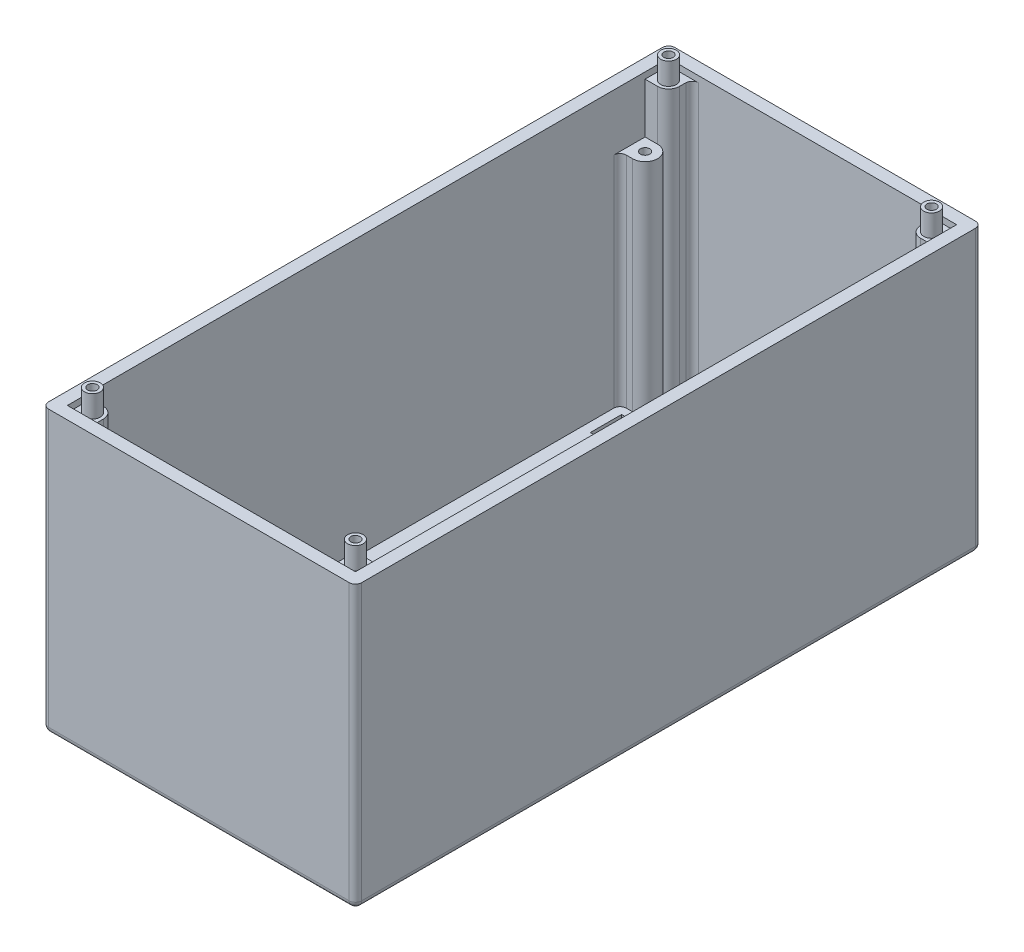
SolidWorks part; units mm, degrees
ref_plane "Front Plane" through (0, 0, 0) normal (0, 0, 1) x (1, 0, 0)
ref_plane "Top Plane" through (0, 0, 0) normal (0, 1, 0) x (1, 0, 0)
ref_plane "Right Plane" through (0, 0, 0) normal (1, 0, 0) x (0, 0, -1)
sketch "Sketch1" plane through (0, 0, 0) normal (0, 1, 0) x (1, 0, 0)
  line L1 (50, -100) -> (-50, -100)
  line L2 (50, -100) -> (50, 100)
  line L3 (50, 100) -> (-50, 100)
  line L4 (-50, -100) -> (-50, 100)
  line L5 (50, -100) -> (-50, 100) construction
  line L6 (50, 100) -> (-50, -100) construction
  point P0 (0, 0)
  dimension "D1" = 200
  dimension "D2" = 100
extrude "Boss-Extrude1" add sketch "Sketch1" along normal blind 2
sketch "Sketch3" plane through (0, 2, 0) normal (0, 1, 0) x (1, 0, 0)
  line L1 (-50, 100) -> (50, 100)
  line L2 (-50, 100) -> (-50, -100)
  line L3 (-50, -100) -> (50, -100)
  line L4 (50, 100) -> (50, -100)
  line L5 (-46, 96) -> (-46, -96)
  line L6 (-46, -96) -> (46, -96)
  line L7 (46, 96) -> (46, -96)
  line L8 (-46, 96) -> (46, 96)
  point P25 (-50, 100)
  dimension "D1" = 4
extrude "Boss-Extrude2" add sketch "Sketch3" along normal blind 88
sketch "Sketch16" plane through (0, 2, 0) normal (0, 1, 0) x (1, 0, 0)
  line L0 (46, 96) -> (-46, 96) construction
  line L1 (-46, -96) -> (46, -96) construction
  line L2 (-46, 96) -> (-46, -96) construction
  line L3 (-46, 96) -> (-46, -96) construction
  line L4 (46, 96) -> (-46, 96) construction
  line L8 (46, -96) -> (46, 96) construction
  line L9 (-46, -96) -> (46, -96) construction
  line L11 (46, -96) -> (46, 96) construction
  circle A4 centre (-42, 92) radius 3.5
  circle A5 centre (42, 92) radius 3.5
  circle A6 centre (42, -92) radius 3.5
  circle A7 centre (-42, -92) radius 3.5
  dimension "D1" = 4
  dimension "D2" = 4
  dimension "D4" = 4
  dimension "D7" = 7
  dimension "D3" = 4
  dimension "D5" = 4
  dimension "D6" = 4
  dimension "D8" = 4
  dimension "D9" = 4
extrude "Boss-Extrude3" add sketch "Sketch16" along normal blind 86
fillet "Fillet2" radius 2 4 edges at (50, 0, 0) (0, 0, 100) (-50, 0, 0) (0, 0, -100)
sketch "Sketch17" plane through (0, 2, 0) normal (0, 1, 0) x (1, 0, 0)
  line L0 (-38.5, 92) -> (-38.5, 96)
  line L1 (46, 96) -> (-46, 96) construction
  line L2 (-38.5, 96) -> (-46, 96)
  line L3 (-46, 96) -> (-46, 88.5)
  line L4 (-46, 96) -> (-46, -96) construction
  line L5 (-46, 88.5) -> (-42, 88.5)
  line L6 (-42, 88.5) -> (-38.5, 92)
  line L7 (38.5, 92) -> (38.5, 96)
  line L8 (46, 96) -> (-46, 96) construction
  line L9 (38.5, 96) -> (46, 96)
  line L10 (46, 96) -> (46, 88.5)
  line L11 (46, -96) -> (46, 96) construction
  line L12 (46, 88.5) -> (42, 88.5)
  line L13 (42, 88.5) -> (38.5, 92)
  line L14 (-38.5, -92) -> (-38.5, -96)
  line L15 (-46, -96) -> (46, -96) construction
  line L16 (-38.5, -96) -> (-46, -96)
  line L17 (-46, -96) -> (-46, -88.5)
  line L18 (-46, 96) -> (-46, -96) construction
  line L19 (-46, -88.5) -> (-42, -88.5)
  line L20 (-42, -88.5) -> (-38.5, -92)
  line L21 (46, -96) -> (38.5, -96)
  line L22 (-46, -96) -> (46, -96) construction
  line L23 (38.5, -96) -> (38.5, -92)
  line L24 (38.5, -92) -> (42, -88.5)
  line L25 (42, -88.5) -> (46, -88.5)
  line L26 (46, -96) -> (46, 96) construction
  line L27 (46, -88.5) -> (46, -96)
  circle A0 centre (-42, 92) radius 3.5 construction
  circle A1 centre (-42, 92) radius 3.5 construction
  circle A2 centre (42, 92) radius 3.5 construction
  circle A3 centre (42, 92) radius 3.5 construction
  circle A4 centre (-42, -92) radius 3.5 construction
  circle A5 centre (-42, -92) radius 3.5 construction
  circle A6 centre (42, -92) radius 3.5 construction
  circle A7 centre (42, -92) radius 3.5 construction
  dimension "D1" = 4
  dimension "D2" = 4
  dimension "D3" = 4
  dimension "D4" = 4
  dimension "D5" = 4
  dimension "D6" = 4
extrude "Boss-Extrude4" add sketch "Sketch17" along normal blind 86
sketch "Sketch20" plane through (0, 2, 0) normal (0, 1, 0) x (1, 0, 0)
  line L0 (-46, 88.5) -> (-42, 88.5)
  line L1 (-46, 88.5) -> (-46, 80.5)
  line L2 (-46, 88.5) -> (-46, -88.5) construction
  line L3 (-46, 80.5) -> (-42, 80.5)
  line L4 (46, 88.5) -> (42, 88.5)
  line L5 (42, 88.5) -> (46, 88.5) construction
  line L6 (46, 88.5) -> (46, 80.5)
  line L7 (46, 80.5) -> (42, 80.5)
  line L8 (-46, -88.5) -> (-42, -88.5)
  line L9 (-46, -88.5) -> (-46, -80.491)
  line L10 (-46, -80.491) -> (-42, -80.491)
  line L11 (46, -88.5) -> (42, -88.5)
  line L12 (46, -88.5) -> (46, -80.5)
  line L13 (46, -96) -> (46, 96) construction
  line L14 (46, -80.5) -> (42, -80.5)
  arc A0 (-42, 88.5) -> (-42, 80.5) centre (-42, 84.5) cw
  circle A1 centre (42, 92) radius 3.5 construction
  arc A2 (42, 88.5) -> (42, 80.5) centre (42, 84.5) ccw
  arc A3 (-42, -80.491) -> (-42, -88.5) centre (-42, -84.4955) cw
  arc A4 (42, -80.5) -> (42, -88.5) centre (42, -84.5) ccw
  dimension "D2" = 4
  dimension "D3" = 4.0045
  dimension "D1" = 8
  dimension "D4" = 8
extrude "Boss-Extrude5" add sketch "Sketch20" along normal blind 70
sketch "Sketch21" plane through (0, 72, 0) normal (0, 1, 0) x (1, 0, 0)
  circle A0 centre (-42, 84.5) radius 1.5
  circle A1 centre (42, 84.5) radius 1.5
  circle A2 centre (42, -84.5) radius 1.5
  circle A3 centre (-42, -84.4955) radius 1.5
  dimension "D1" = 3
  dimension "D2" = 3
  dimension "D3" = 3
  dimension "D4" = 3
extrude "Cut-Extrude3" cut sketch "Sketch21" against normal blind 13
fillet "Fillet4" radius 2 8 edges at (49.4142, 0.5858, 99.4142) (-49.4142, 0.5858, 99.4142) (-49.4142, 0.5858, -99.4142) (49.4142, 0.5858, -99.4142) (50, 46, 100) (-50, 46, 100) (-50, 46, -100) (50, 46, -100)
sketch "Sketch22" plane through (0, 2, 0) normal (0, 1, 0) x (1, 0, 0)
  circle A0 centre (-42, 92) radius 2.75
  circle A1 centre (42, 92) radius 2.75
  circle A2 centre (42, -92) radius 2.75
  circle A3 centre (-42, -92) radius 2.75
  dimension "D1" = 5.5
  dimension "D2" = 5.5
  dimension "D3" = 5.5
  dimension "D4" = 5.5
extrude "Cut-Extrude4" cut sketch "Sketch22" against normal blind 2 and the other way blind 83
sketch "Sketch24" plane through (0, 88, 0) normal (0, 1, 0) x (1, 0, 0)
  circle A0 centre (-42, 92) radius 2.5
  circle A1 centre (42, 92) radius 2.5
  circle A2 centre (42, -92) radius 2.5
  circle A3 centre (-42, -92) radius 2.5
  dimension "D1" = 5
  dimension "D2" = 5
  dimension "D3" = 5
  dimension "D4" = 5
extrude "Boss-Extrude6" add sketch "Sketch24" along normal blind 7
sketch "Sketch25" plane through (0, 85, 0) normal (0, -1, 0) x (1, 0, 0)
  circle A0 centre (-42, 92) radius 1.5
  circle A1 centre (42, 92) radius 1.5
  circle A2 centre (-42, -92) radius 1.5
  circle A3 centre (42, -92) radius 1.5
  dimension "D1" = 3
  dimension "D2" = 3
  dimension "D3" = 3
  dimension "D4" = 3
extrude "Cut-Extrude5" cut sketch "Sketch25" against normal blind 10
fillet "Fillet5" radius 2 8 edges at (46, 37, -80.5) (38.5, 45, -96) (-38.5, 45, -96) (-46, 37, -80.5) (-46, 37, 80.491) (-38.5, 45, 96) (46, 37, 80.5) (38.5, 45, 96)
sketch "Sketch26" plane through (0, 2, 0) normal (0, 1, 0) x (1, 0, 0)
  line L0 (-36.5, -96) -> (36.5, -96) construction
  line L1 (46, -78.5) -> (46, 78.5) construction
  line L2 (-46, 78.5) -> (-46, -78.491) construction
  line L3 (36.5, 96) -> (-36.5, 96) construction
  circle A0 centre (29, -78) radius 3.5
  circle A1 centre (29, -64) radius 3.5
  circle A2 centre (31, 85) radius 3.25
  circle A3 centre (-16, -78) radius 3.5
  dimension "D1" = 7
  dimension "D2" = 7
  dimension "D3" = 18
  dimension "D7" = 6.5
  dimension "D9" = 15
  dimension "D10" = 7
  dimension "D11" = 18
  dimension "D4" = 32
  dimension "D5" = 17
  dimension "D6" = 17
  dimension "D8" = 11
  dimension "D12" = 30
extrude "Cut-Extrude6" cut sketch "Sketch26" against normal blind 2
sketch "Sketch27" plane through (0, 0, 0) normal (0, -1, 0) x (1, 0, 0)
  line L0 (-48, -98) -> (48, -98) construction
  line L1 (-43, -68) -> (-17, -68)
  line L2 (-43, -68) -> (-43, -78)
  line L3 (-43, -78) -> (-17, -78)
  line L4 (-17, -68) -> (-17, -78)
  line L5 (-48, 98) -> (-48, -98) construction
  point P8 (-43, -73)
  dimension "D1" = 26
  dimension "D2" = 10
  dimension "D3" = 20
  dimension "D4" = 5
extrude "Cut-Extrude7" cut sketch "Sketch27" against normal blind 2
sketch "Sketch28" plane through (0, 0, 0) normal (0, -1, 0) x (1, 0, 0)
  line L0 (48, -98) -> (48, 98) construction
  line L2 (39, -62) -> (39, -76)
  line L4 (41, -62) -> (41, -76)
  line L13 (-48, -98) -> (48, -98) construction
  line L15 (34, -62) -> (34, -76)
  line L17 (36, -62) -> (36, -76)
  line L19 (29, -62) -> (29, -76)
  line L21 (31, -62) -> (31, -76)
  line L23 (24, -62) -> (24, -76)
  line L25 (26, -62) -> (26, -76)
  line L27 (19, -62) -> (19, -76)
  line L29 (21, -62) -> (21, -76)
  line L31 (14, -62) -> (14, -76)
  line L33 (16, -62) -> (16, -76)
  line L35 (9, -62) -> (9, -76)
  line L37 (11, -62) -> (11, -76)
  line L39 (4, -62) -> (4, -76)
  line L41 (6, -62) -> (6, -76)
  line L43 (-1, -62) -> (-1, -76)
  line L45 (1, -62) -> (1, -76)
  line L47 (-6, -62) -> (-6, -76)
  line L49 (-4, -62) -> (-4, -76)
  line L50 (39, 33) -> (39, 19)
  line L52 (39, -43) -> (39, -57)
  line L54 (41, -43) -> (41, -57)
  line L56 (34, -43) -> (34, -57)
  line L58 (36, -43) -> (36, -57)
  line L60 (29, -43) -> (29, -57)
  line L62 (31, -43) -> (31, -57)
  line L64 (24, -43) -> (24, -57)
  line L66 (26, -43) -> (26, -57)
  line L68 (19, -43) -> (19, -57)
  line L70 (21, -43) -> (21, -57)
  line L72 (14, -43) -> (14, -57)
  line L74 (16, -43) -> (16, -57)
  line L76 (9, -43) -> (9, -57)
  line L78 (11, -43) -> (11, -57)
  line L80 (4, -43) -> (4, -57)
  line L82 (6, -43) -> (6, -57)
  line L84 (-1, -43) -> (-1, -57)
  line L86 (1, -43) -> (1, -57)
  line L88 (-6, -43) -> (-6, -57)
  line L90 (-4, -43) -> (-4, -57)
  line L92 (39, -24) -> (39, -38)
  line L94 (41, -24) -> (41, -38)
  line L96 (34, -24) -> (34, -38)
  line L98 (36, -24) -> (36, -38)
  line L100 (29, -24) -> (29, -38)
  line L102 (31, -24) -> (31, -38)
  line L104 (24, -24) -> (24, -38)
  line L106 (26, -24) -> (26, -38)
  line L108 (19, -24) -> (19, -38)
  line L110 (21, -24) -> (21, -38)
  line L112 (14, -24) -> (14, -38)
  line L114 (16, -24) -> (16, -38)
  line L116 (9, -24) -> (9, -38)
  line L118 (11, -24) -> (11, -38)
  line L120 (4, -24) -> (4, -38)
  line L122 (6, -24) -> (6, -38)
  line L124 (-1, -24) -> (-1, -38)
  line L126 (1, -24) -> (1, -38)
  line L128 (-6, -24) -> (-6, -38)
  line L130 (-4, -24) -> (-4, -38)
  line L132 (39, -5) -> (39, -19)
  line L134 (41, -5) -> (41, -19)
  line L136 (34, -5) -> (34, -19)
  line L138 (36, -5) -> (36, -19)
  line L140 (29, -5) -> (29, -19)
  line L142 (31, -5) -> (31, -19)
  line L144 (24, -5) -> (24, -19)
  line L146 (26, -5) -> (26, -19)
  line L148 (19, -5) -> (19, -19)
  line L150 (21, -5) -> (21, -19)
  line L152 (14, -5) -> (14, -19)
  line L154 (16, -5) -> (16, -19)
  line L156 (9, -5) -> (9, -19)
  line L158 (11, -5) -> (11, -19)
  line L160 (4, -5) -> (4, -19)
  line L162 (6, -5) -> (6, -19)
  line L164 (-1, -5) -> (-1, -19)
  line L166 (1, -5) -> (1, -19)
  line L168 (-6, -5) -> (-6, -19)
  line L170 (-4, -5) -> (-4, -19)
  line L172 (39, 14) -> (39, 0)
  line L174 (41, 14) -> (41, 0)
  line L176 (34, 14) -> (34, 0)
  line L178 (36, 14) -> (36, 0)
  line L180 (29, 14) -> (29, 0)
  line L182 (31, 14) -> (31, 0)
  line L184 (24, 14) -> (24, 0)
  line L186 (26, 14) -> (26, 0)
  line L188 (19, 14) -> (19, 0)
  line L190 (21, 14) -> (21, 0)
  line L192 (14, 14) -> (14, 0)
  line L194 (16, 14) -> (16, 0)
  line L196 (9, 14) -> (9, 0)
  line L198 (11, 14) -> (11, 0)
  line L200 (4, 14) -> (4, 0)
  line L202 (6, 14) -> (6, 0)
  line L204 (-1, 14) -> (-1, 0)
  line L206 (1, 14) -> (1, 0)
  line L208 (-6, 14) -> (-6, 0)
  line L210 (-4, 14) -> (-4, 0)
  line L211 (41, 33) -> (41, 19)
  line L212 (34, 33) -> (34, 19)
  line L213 (36, 33) -> (36, 19)
  line L214 (29, 33) -> (29, 19)
  line L215 (31, 33) -> (31, 19)
  line L216 (24, 33) -> (24, 19)
  line L217 (26, 33) -> (26, 19)
  line L218 (19, 33) -> (19, 19)
  line L219 (21, 33) -> (21, 19)
  line L220 (14, 33) -> (14, 19)
  line L221 (16, 33) -> (16, 19)
  line L222 (9, 33) -> (9, 19)
  line L223 (11, 33) -> (11, 19)
  line L224 (4, 33) -> (4, 19)
  line L225 (6, 33) -> (6, 19)
  line L226 (-1, 33) -> (-1, 19)
  line L227 (1, 33) -> (1, 19)
  line L228 (-6, 33) -> (-6, 19)
  line L229 (-4, 33) -> (-4, 19)
  line L230 (39, 52) -> (39, 38)
  line L231 (41, 52) -> (41, 38)
  line L232 (34, 52) -> (34, 38)
  line L233 (36, 52) -> (36, 38)
  line L234 (29, 52) -> (29, 38)
  line L235 (31, 52) -> (31, 38)
  line L236 (24, 52) -> (24, 38)
  line L237 (26, 52) -> (26, 38)
  line L238 (19, 52) -> (19, 38)
  line L239 (21, 52) -> (21, 38)
  line L240 (14, 52) -> (14, 38)
  line L241 (16, 52) -> (16, 38)
  line L242 (9, 52) -> (9, 38)
  line L243 (11, 52) -> (11, 38)
  line L244 (4, 52) -> (4, 38)
  line L245 (6, 52) -> (6, 38)
  line L246 (-1, 52) -> (-1, 38)
  line L247 (1, 52) -> (1, 38)
  line L248 (-6, 52) -> (-6, 38)
  line L249 (-4, 52) -> (-4, 38)
  arc A0 (39, -62) -> (41, -62) centre (40, -62) cw
  arc A1 (34, -62) -> (36, -62) centre (35, -62) cw
  arc A2 (29, -62) -> (31, -62) centre (30, -62) cw
  arc A3 (39, -76) -> (41, -76) centre (40, -76) ccw
  arc A4 (34, -76) -> (36, -76) centre (35, -76) ccw
  arc A5 (29, -76) -> (31, -76) centre (30, -76) ccw
  arc A6 (24, -76) -> (26, -76) centre (25, -76) ccw
  arc A7 (26, -62) -> (24, -62) centre (25, -62) ccw
  arc A8 (21, -62) -> (19, -62) centre (20, -62) ccw
  arc A9 (21, -76) -> (19, -76) centre (20, -76) cw
  arc A10 (16, -76) -> (14, -76) centre (15, -76) cw
  arc A11 (11, -76) -> (9, -76) centre (10, -76) cw
  arc A12 (6, -76) -> (4, -76) centre (5, -76) cw
  arc A13 (1, -76) -> (-1, -76) centre (0, -76) cw
  arc A14 (-4, -76) -> (-6, -76) centre (-5, -76) cw
  arc A15 (-6, -62) -> (-4, -62) centre (-5, -62) cw
  arc A16 (16, -62) -> (14, -62) centre (15, -62) ccw
  arc A17 (11, -62) -> (9, -62) centre (10, -62) ccw
  arc A18 (6, -62) -> (4, -62) centre (5, -62) ccw
  arc A19 (1, -62) -> (-1, -62) centre (0, -62) ccw
  arc A20 (41, -57) -> (39, -57) centre (40, -57) cw
  arc A21 (36, -57) -> (34, -57) centre (35, -57) cw
  arc A22 (31, -57) -> (29, -57) centre (30, -57) cw
  arc A23 (26, -57) -> (24, -57) centre (25, -57) cw
  arc A24 (21, -57) -> (19, -57) centre (20, -57) cw
  arc A25 (16, -57) -> (14, -57) centre (15, -57) cw
  arc A26 (11, -57) -> (9, -57) centre (10, -57) cw
  arc A27 (6, -57) -> (4, -57) centre (5, -57) cw
  arc A28 (1, -57) -> (-1, -57) centre (0, -57) cw
  arc A29 (-4, -57) -> (-6, -57) centre (-5, -57) cw
  arc A30 (41, -43) -> (39, -43) centre (40, -43) ccw
  arc A31 (36, -43) -> (34, -43) centre (35, -43) ccw
  arc A32 (31, -43) -> (29, -43) centre (30, -43) ccw
  arc A33 (26, -43) -> (24, -43) centre (25, -43) ccw
  arc A34 (21, -43) -> (19, -43) centre (20, -43) ccw
  arc A35 (16, -43) -> (14, -43) centre (15, -43) ccw
  arc A36 (11, -43) -> (9, -43) centre (10, -43) ccw
  arc A37 (6, -43) -> (4, -43) centre (5, -43) ccw
  arc A38 (1, -43) -> (-1, -43) centre (0, -43) ccw
  arc A39 (-4, -43) -> (-6, -43) centre (-5, -43) ccw
  arc A40 (41, -38) -> (39, -38) centre (40, -38) cw
  arc A41 (36, -38) -> (34, -38) centre (35, -38) cw
  arc A42 (31, -38) -> (29, -38) centre (30, -38) cw
  arc A43 (26, -38) -> (24, -38) centre (25, -38) cw
  arc A44 (21, -38) -> (19, -38) centre (20, -38) cw
  arc A45 (16, -38) -> (14, -38) centre (15, -38) cw
  arc A46 (11, -38) -> (9, -38) centre (10, -38) cw
  arc A47 (6, -38) -> (4, -38) centre (5, -38) cw
  arc A48 (-4, -38) -> (-6, -38) centre (-5, -38) cw
  arc A49 (1, -38) -> (-1, -38) centre (0, -38) cw
  arc A50 (-6, -24) -> (-4, -24) centre (-5, -24) cw
  arc A51 (-1, -24) -> (1, -24) centre (0, -24) cw
  arc A52 (4, -24) -> (6, -24) centre (5, -24) cw
  arc A53 (9, -24) -> (11, -24) centre (10, -24) cw
  arc A54 (14, -24) -> (16, -24) centre (15, -24) cw
  arc A55 (19, -24) -> (21, -24) centre (20, -24) cw
  arc A56 (24, -24) -> (26, -24) centre (25, -24) cw
  arc A57 (29, -24) -> (31, -24) centre (30, -24) cw
  arc A58 (34, -24) -> (36, -24) centre (35, -24) cw
  arc A59 (39, -24) -> (41, -24) centre (40, -24) cw
  arc A60 (39, -19) -> (41, -19) centre (40, -19) ccw
  arc A61 (34, -19) -> (36, -19) centre (35, -19) ccw
  arc A62 (29, -19) -> (31, -19) centre (30, -19) ccw
  arc A63 (24, -19) -> (26, -19) centre (25, -19) ccw
  arc A64 (19, -19) -> (21, -19) centre (20, -19) ccw
  arc A65 (-6, -19) -> (-4, -19) centre (-5, -19) ccw
  arc A66 (-1, -19) -> (1, -19) centre (0, -19) ccw
  arc A67 (4, -19) -> (6, -19) centre (5, -19) ccw
  arc A68 (9, -19) -> (11, -19) centre (10, -19) ccw
  arc A69 (14, -19) -> (16, -19) centre (15, -19) ccw
  arc A70 (-6, -5) -> (-4, -5) centre (-5, -5) cw
  arc A71 (-1, -5) -> (1, -5) centre (0, -5) cw
  arc A72 (4, -5) -> (6, -5) centre (5, -5) cw
  arc A73 (9, -5) -> (11, -5) centre (10, -5) cw
  arc A74 (14, -5) -> (16, -5) centre (15, -5) cw
  arc A75 (41, -5) -> (39, -5) centre (40, -5) ccw
  arc A76 (36, -5) -> (34, -5) centre (35, -5) ccw
  arc A77 (31, -5) -> (29, -5) centre (30, -5) ccw
  arc A78 (26, -5) -> (24, -5) centre (25, -5) ccw
  arc A79 (21, -5) -> (19, -5) centre (20, -5) ccw
  arc A80 (41, 14) -> (39, 14) centre (40, 14) ccw
  arc A81 (36, 14) -> (34, 14) centre (35, 14) ccw
  arc A82 (31, 14) -> (29, 14) centre (30, 14) ccw
  arc A83 (39, 0) -> (41, 0) centre (40, 0) ccw
  arc A84 (34, 0) -> (36, 0) centre (35, 0) ccw
  arc A85 (29, 0) -> (31, 0) centre (30, 0) ccw
  arc A86 (24, 0) -> (26, 0) centre (25, 0) ccw
  arc A87 (19, 0) -> (21, 0) centre (20, 0) ccw
  arc A88 (14, 0) -> (16, 0) centre (15, 0) ccw
  arc A89 (24, 14) -> (26, 14) centre (25, 14) cw
  arc A90 (19, 14) -> (21, 14) centre (20, 14) cw
  arc A91 (14, 14) -> (16, 14) centre (15, 14) cw
  arc A92 (9, 14) -> (11, 14) centre (10, 14) cw
  arc A93 (4, 14) -> (6, 14) centre (5, 14) cw
  arc A94 (9, 0) -> (11, 0) centre (10, 0) ccw
  arc A95 (4, 0) -> (6, 0) centre (5, 0) ccw
  arc A96 (-1, 14) -> (1, 14) centre (0, 14) cw
  arc A97 (-6, 14) -> (-4, 14) centre (-5, 14) cw
  arc A98 (-6, 0) -> (-4, 0) centre (-5, 0) ccw
  arc A99 (-1, 0) -> (1, 0) centre (0, 0) ccw
  arc A100 (41, 33) -> (39, 33) centre (40, 33) ccw
  arc A101 (36, 33) -> (34, 33) centre (35, 33) ccw
  arc A102 (31, 33) -> (29, 33) centre (30, 33) ccw
  arc A103 (39, 19) -> (41, 19) centre (40, 19) ccw
  arc A104 (34, 19) -> (36, 19) centre (35, 19) ccw
  arc A105 (29, 19) -> (31, 19) centre (30, 19) ccw
  arc A106 (24, 19) -> (26, 19) centre (25, 19) ccw
  arc A107 (19, 19) -> (21, 19) centre (20, 19) ccw
  arc A108 (14, 19) -> (16, 19) centre (15, 19) ccw
  arc A109 (24, 33) -> (26, 33) centre (25, 33) cw
  arc A110 (19, 33) -> (21, 33) centre (20, 33) cw
  arc A111 (14, 33) -> (16, 33) centre (15, 33) cw
  arc A112 (9, 33) -> (11, 33) centre (10, 33) cw
  arc A113 (4, 33) -> (6, 33) centre (5, 33) cw
  arc A114 (9, 19) -> (11, 19) centre (10, 19) ccw
  arc A115 (4, 19) -> (6, 19) centre (5, 19) ccw
  arc A116 (-1, 33) -> (1, 33) centre (0, 33) cw
  arc A117 (-6, 33) -> (-4, 33) centre (-5, 33) cw
  arc A118 (-6, 19) -> (-4, 19) centre (-5, 19) ccw
  arc A119 (-1, 19) -> (1, 19) centre (0, 19) ccw
  arc A120 (41, 52) -> (39, 52) centre (40, 52) ccw
  arc A121 (36, 52) -> (34, 52) centre (35, 52) ccw
  arc A122 (31, 52) -> (29, 52) centre (30, 52) ccw
  arc A123 (39, 38) -> (41, 38) centre (40, 38) ccw
  arc A124 (34, 38) -> (36, 38) centre (35, 38) ccw
  arc A125 (29, 38) -> (31, 38) centre (30, 38) ccw
  arc A126 (24, 38) -> (26, 38) centre (25, 38) ccw
  arc A127 (19, 38) -> (21, 38) centre (20, 38) ccw
  arc A128 (14, 38) -> (16, 38) centre (15, 38) ccw
  arc A129 (24, 52) -> (26, 52) centre (25, 52) cw
  arc A130 (19, 52) -> (21, 52) centre (20, 52) cw
  arc A131 (14, 52) -> (16, 52) centre (15, 52) cw
  arc A132 (9, 52) -> (11, 52) centre (10, 52) cw
  arc A133 (4, 52) -> (6, 52) centre (5, 52) cw
  arc A134 (9, 38) -> (11, 38) centre (10, 38) ccw
  arc A135 (4, 38) -> (6, 38) centre (5, 38) ccw
  arc A136 (-1, 52) -> (1, 52) centre (0, 52) cw
  arc A137 (-6, 52) -> (-4, 52) centre (-5, 52) cw
  arc A138 (-6, 38) -> (-4, 38) centre (-5, 38) ccw
  arc A139 (-1, 38) -> (1, 38) centre (0, 38) ccw
  dimension "D233" = 1
  dimension "D235" = 3
  dimension "D243" = 5
  dimension "D1" = 7
  dimension "D3" = 2
  dimension "D4" = 14
  dimension "D5" = 3
  dimension "D7" = 2
  dimension "D8" = 14
  dimension "D9" = 14
  dimension "D10" = 3
  dimension "D12" = 14
  dimension "D13" = 3
  dimension "D14" = 2
  dimension "D15" = 2
  dimension "D17" = 2
  dimension "D18" = 14
  dimension "D19" = 3
  dimension "D20" = 5
  dimension "D21" = 2
  dimension "D22" = 14
  dimension "D23" = 14
  dimension "D24" = 3
  dimension "D25" = 22
  dimension "D26" = 14
  dimension "D27" = 3
  dimension "D28" = 2
  dimension "D29" = 2
  dimension "D30" = 3
  dimension "D31" = 3
  dimension "D32" = 3
  dimension "D33" = 3
  dimension "D34" = 3
  dimension "D35" = 2
  dimension "D36" = 3
  dimension "D37" = 14
  dimension "D38" = 2
  dimension "D39" = 3
  dimension "D40" = 2
  dimension "D41" = 14
  dimension "D42" = 3
  dimension "D43" = 3
  dimension "D44" = 2
  dimension "D45" = 14
  dimension "D46" = 14
  dimension "D47" = 3
  dimension "D48" = 3
  dimension "D49" = 14
  dimension "D50" = 3
  dimension "D51" = 2
  dimension "D52" = 2
  dimension "D53" = 3
  dimension "D54" = 2
  dimension "D55" = 14
  dimension "D56" = 3
  dimension "D57" = 3
  dimension "D58" = 2
  dimension "D59" = 14
  dimension "D60" = 14
  dimension "D61" = 3
  dimension "D62" = 3
  dimension "D63" = 14
  dimension "D64" = 3
  dimension "D65" = 2
  dimension "D66" = 2
  dimension "D67" = 3
  dimension "D68" = 3
  dimension "D69" = 3
  dimension "D70" = 3
  dimension "D71" = 3
  dimension "D72" = 2
  dimension "D73" = 3
  dimension "D74" = 14
  dimension "D75" = 2
  dimension "D76" = 7
  dimension "D77" = 3
  dimension "D78" = 3
  dimension "D79" = 3
  dimension "D80" = 2
  dimension "D81" = 14
  dimension "D82" = 3
  dimension "D83" = 3
  dimension "D84" = 2
  dimension "D85" = 14
  dimension "D86" = 14
  dimension "D87" = 3
  dimension "D88" = 3
  dimension "D89" = 14
  dimension "D90" = 3
  dimension "D91" = 2
  dimension "D92" = 2
  dimension "D93" = 3
  dimension "D94" = 2
  dimension "D95" = 14
  dimension "D96" = 3
  dimension "D97" = 3
  dimension "D98" = 2
  dimension "D99" = 14
  dimension "D100" = 14
  dimension "D101" = 3
  dimension "D102" = 3
  dimension "D103" = 14
  dimension "D104" = 3
  dimension "D105" = 2
  dimension "D106" = 2
  dimension "D107" = 5
  dimension "D108" = 3
  dimension "D109" = 5
  dimension "D110" = 3
  dimension "D111" = 3
  dimension "D112" = 2
  dimension "D113" = 5
  dimension "D114" = 14
  dimension "D115" = 2
  dimension "D116" = 2
  dimension "D117" = 14
  dimension "D118" = 3
  dimension "D119" = 3
  dimension "D120" = 2
  dimension "D121" = 14
  dimension "D122" = 14
  dimension "D123" = 3
  dimension "D124" = 3
  dimension "D125" = 14
  dimension "D126" = 3
  dimension "D127" = 2
  dimension "D128" = 2
  dimension "D129" = 3
  dimension "D130" = 2
  dimension "D131" = 14
  dimension "D132" = 3
  dimension "D133" = 3
  dimension "D134" = 2
  dimension "D135" = 14
  dimension "D136" = 14
  dimension "D137" = 3
  dimension "D138" = 3
  dimension "D139" = 14
  dimension "D140" = 3
  dimension "D141" = 2
  dimension "D142" = 2
  dimension "D143" = 3
  dimension "D144" = 3
  dimension "D145" = 3
  dimension "D146" = 3
  dimension "D147" = 3
  dimension "D148" = 2
  dimension "D149" = 3
  dimension "D150" = 14
  dimension "D151" = 2
  dimension "D152" = 3
  dimension "D153" = 3
  dimension "D154" = 3
  dimension "D155" = 3
  dimension "D156" = 7
  dimension "D157" = 7
  dimension "D158" = 3
  dimension "D159" = 3
  dimension "D160" = 2
  dimension "D161" = 14
  dimension "D162" = 3
  dimension "D163" = 2
  dimension "D164" = 14
  dimension "D165" = 14
  dimension "D166" = 3
  dimension "D167" = 14
  dimension "D168" = 3
  dimension "D169" = 2
  dimension "D170" = 14
  dimension "D171" = 3
  dimension "D172" = 2
  dimension "D173" = 14
  dimension "D174" = 14
  dimension "D175" = 3
  dimension "D176" = 14
  dimension "D177" = 3
  dimension "D178" = 3
  dimension "D179" = 14
  dimension "D180" = 7
  dimension "D181" = 2
  dimension "D182" = 3
  dimension "D183" = 2
  dimension "D184" = 2
  dimension "D185" = 3
  dimension "D186" = 2
  dimension "D187" = 2
  dimension "D188" = 2
  dimension "D189" = 3
  dimension "D190" = 3
  dimension "D191" = 3
  dimension "D192" = 3
  dimension "D193" = 14
  dimension "D194" = 3
  dimension "D195" = 3
  dimension "D196" = 3
  dimension "D197" = 3
  dimension "D198" = 3
  dimension "D199" = 3
  dimension "D200" = 3
  dimension "D201" = 3
  dimension "D202" = 3
  dimension "D203" = 3
  dimension "D204" = 14
  dimension "D205" = 3
  dimension "D206" = 2
  dimension "D207" = 14
  dimension "D208" = 14
  dimension "D209" = 3
  dimension "D210" = 14
  dimension "D211" = 3
  dimension "D212" = 14
  dimension "D213" = 3
  dimension "D214" = 2
  dimension "D215" = 14
  dimension "D216" = 14
  dimension "D217" = 3
  dimension "D218" = 14
  dimension "D219" = 3
  dimension "D220" = 3
  dimension "D221" = 14
  dimension "D222" = 3
  dimension "D223" = 3
  dimension "D224" = 14
  dimension "D225" = 7
  dimension "D226" = 2
  dimension "D227" = 2
  dimension "D228" = 2
  dimension "D229" = 2
  dimension "D230" = 2
  dimension "D231" = 2
  dimension "D232" = 2
  dimension "D234" = 3
  dimension "D236" = 3
  dimension "D237" = 3
  dimension "D238" = 3
  dimension "D239" = 3
  dimension "D240" = 3
  dimension "D241" = 3
  dimension "D242" = 3
  dimension "D244" = 14
  dimension "D245" = 3
  dimension "D246" = 2
  dimension "D247" = 14
  dimension "D248" = 14
  dimension "D249" = 3
  dimension "D250" = 14
  dimension "D251" = 3
  dimension "D252" = 14
  dimension "D253" = 3
  dimension "D254" = 2
  dimension "D255" = 14
  dimension "D256" = 14
  dimension "D257" = 3
  dimension "D258" = 14
  dimension "D259" = 3
  dimension "D260" = 3
  dimension "D261" = 14
  dimension "D262" = 3
  dimension "D263" = 3
  dimension "D264" = 14
  dimension "D265" = 7
  dimension "D266" = 2
  dimension "D267" = 2
  dimension "D268" = 2
  dimension "D269" = 2
  dimension "D270" = 2
  dimension "D271" = 2
  dimension "D272" = 2
  dimension "D273" = 2
  dimension "D274" = 5
  dimension "D275" = 5
  dimension "D276" = 5
  dimension "D277" = 5
  dimension "D278" = 5
  dimension "D279" = 5
  dimension "D280" = 5
  dimension "D281" = 5
  dimension "D282" = 5
  dimension "D283" = 5
  dimension "D284" = 14
extrude "Cut-Extrude8" cut sketch "Sketch28" against normal blind 1
sketch "Sketch29" plane through (0, 0, 0) normal (0, -1, 0) x (1, 0, 0)
  line L0 (24, -62) -> (24, -76) construction
  line L1 (39, -76) -> (40, -76)
  line L2 (39, -76) -> (39, -62)
  line L3 (39, -62) -> (40, -62)
  line L4 (40, -76) -> (40, -62)
  line L5 (34, -76) -> (35, -76)
  line L6 (34, -76) -> (34, -62)
  line L7 (34, -62) -> (35, -62)
  line L8 (35, -76) -> (35, -62)
  line L9 (29, -62) -> (30, -62)
  line L10 (29, -62) -> (29, -76)
  line L11 (29, -76) -> (30, -76)
  line L12 (30, -62) -> (30, -76)
  line L13 (24, -62) -> (25, -62)
  line L14 (24, -62) -> (24, -76)
  line L15 (24, -76) -> (25, -76)
  line L16 (25, -62) -> (25, -76)
  line L17 (24, -62) -> (24, -76) construction
  line L18 (-1, -62) -> (-1, -76) construction
  line L19 (19, -62) -> (20, -62)
  line L20 (19, -62) -> (19, -76)
  line L21 (19, -76) -> (20, -76)
  line L22 (20, -62) -> (20, -76)
  line L23 (14, -62) -> (15, -62)
  line L24 (14, -62) -> (14, -76)
  line L25 (14, -76) -> (15, -76)
  line L26 (15, -62) -> (15, -76)
  line L27 (9, -62) -> (10, -62)
  line L28 (9, -62) -> (9, -76)
  line L29 (9, -76) -> (10, -76)
  line L30 (10, -62) -> (10, -76)
  line L31 (4, -62) -> (5, -62)
  line L32 (4, -62) -> (4, -76)
  line L33 (4, -76) -> (5, -76)
  line L34 (5, -62) -> (5, -76)
  line L35 (-1, -62) -> (0, -62)
  line L36 (-1, -62) -> (-1, -76)
  line L37 (-1, -76) -> (0, -76)
  line L38 (0, -62) -> (0, -76)
  line L39 (-6, -43) -> (-6, -57) construction
  line L40 (-6, -62) -> (-5, -62)
  line L41 (-6, -62) -> (-6, -76)
  line L42 (-6, -76) -> (-5, -76)
  line L43 (-5, -62) -> (-5, -76)
  line L44 (39, -43) -> (40, -43)
  line L45 (39, -43) -> (39, -57)
  line L46 (39, -57) -> (40, -57)
  line L47 (40, -43) -> (40, -57)
  line L48 (34, -43) -> (35, -43)
  line L49 (34, -43) -> (34, -57)
  line L50 (34, -57) -> (35, -57)
  line L51 (35, -43) -> (35, -57)
  line L52 (29, -43) -> (30, -43)
  line L53 (29, -43) -> (29, -57)
  line L54 (29, -57) -> (30, -57)
  line L55 (30, -43) -> (30, -57)
  line L56 (24, -43) -> (25, -43)
  line L57 (24, -43) -> (24, -57)
  line L58 (24, -57) -> (25, -57)
  line L59 (25, -43) -> (25, -57)
  line L60 (19, -43) -> (20, -43)
  line L61 (19, -43) -> (19, -57)
  line L62 (19, -57) -> (20, -57)
  line L63 (20, -43) -> (20, -57)
  line L64 (14, -43) -> (15, -43)
  line L65 (14, -43) -> (14, -57)
  line L66 (14, -57) -> (15, -57)
  line L67 (15, -43) -> (15, -57)
  line L68 (9, -43) -> (10, -43)
  line L69 (9, -43) -> (9, -57)
  line L70 (9, -57) -> (10, -57)
  line L71 (10, -43) -> (10, -57)
  line L72 (4, -43) -> (5, -43)
  line L73 (4, -43) -> (4, -57)
  line L74 (4, -57) -> (5, -57)
  line L75 (5, -43) -> (5, -57)
  line L76 (-1, -43) -> (0, -43)
  line L77 (-1, -43) -> (-1, -57)
  line L78 (-1, -57) -> (0, -57)
  line L79 (0, -43) -> (0, -57)
  line L80 (-6, -43) -> (-5, -43)
  line L81 (-6, -43) -> (-6, -57)
  line L82 (-6, -57) -> (-5, -57)
  line L83 (-5, -43) -> (-5, -57)
  line L84 (-6, -43) -> (-6, -57) construction
  line L85 (4, -5) -> (4, -19) construction
  line L86 (39, 14) -> (40, 14)
  line L87 (39, 14) -> (39, 0)
  line L88 (39, 0) -> (40, 0)
  line L89 (40, 14) -> (40, 0)
  line L90 (34, 14) -> (35, 14)
  line L91 (34, 14) -> (34, 0)
  line L92 (34, 0) -> (35, 0)
  line L93 (35, 14) -> (35, 0)
  line L94 (29, 14) -> (30, 14)
  line L95 (29, 14) -> (29, 0)
  line L96 (29, 0) -> (30, 0)
  line L97 (30, 14) -> (30, 0)
  line L98 (24, 14) -> (25, 14)
  line L99 (24, 14) -> (24, 0)
  line L100 (24, 0) -> (25, 0)
  line L101 (25, 14) -> (25, 0)
  line L102 (19, 14) -> (20, 14)
  line L103 (19, 14) -> (19, 0)
  line L104 (19, 0) -> (20, 0)
  line L105 (20, 14) -> (20, 0)
  line L106 (14, 14) -> (15, 14)
  line L107 (14, 14) -> (14, 0)
  line L108 (14, 0) -> (15, 0)
  line L109 (15, 14) -> (15, 0)
  line L110 (9, 14) -> (10, 14)
  line L111 (9, 14) -> (9, 0)
  line L112 (9, 0) -> (10, 0)
  line L113 (10, 14) -> (10, 0)
  line L114 (4, 14) -> (5, 14)
  line L115 (4, 14) -> (4, 0)
  line L116 (4, 0) -> (5, 0)
  line L117 (5, 14) -> (5, 0)
  line L118 (-1, 14) -> (0, 14)
  line L119 (-1, 14) -> (-1, 0)
  line L120 (-1, 0) -> (0, 0)
  line L121 (0, 14) -> (0, 0)
  line L122 (-6, 14) -> (-5, 14)
  line L123 (-6, 14) -> (-6, 0)
  line L124 (-6, 0) -> (-5, 0)
  line L125 (-5, 14) -> (-5, 0)
  line L126 (39, -5) -> (40, -5)
  line L127 (39, -5) -> (39, -19)
  line L128 (39, -19) -> (40, -19)
  line L129 (40, -5) -> (40, -19)
  line L130 (34, -5) -> (35, -5)
  line L131 (34, -5) -> (34, -19)
  line L132 (34, -19) -> (35, -19)
  line L133 (35, -5) -> (35, -19)
  line L134 (29, -5) -> (30, -5)
  line L135 (29, -5) -> (29, -19)
  line L136 (29, -19) -> (30, -19)
  line L137 (30, -5) -> (30, -19)
  line L138 (24, -5) -> (25, -5)
  line L139 (24, -5) -> (24, -19)
  line L140 (24, -19) -> (25, -19)
  line L141 (25, -5) -> (25, -19)
  line L142 (19, -5) -> (20, -5)
  line L143 (19, -5) -> (19, -19)
  line L144 (19, -19) -> (20, -19)
  line L145 (20, -5) -> (20, -19)
  line L146 (14, -5) -> (15, -5)
  line L147 (14, -5) -> (14, -19)
  line L148 (14, -19) -> (15, -19)
  line L149 (15, -5) -> (15, -19)
  line L150 (9, -5) -> (10, -5)
  line L151 (9, -5) -> (9, -19)
  line L152 (9, -19) -> (10, -19)
  line L153 (10, -5) -> (10, -19)
  line L154 (4, -5) -> (5, -5)
  line L155 (4, -5) -> (4, -19)
  line L156 (4, -19) -> (5, -19)
  line L157 (5, -5) -> (5, -19)
  line L158 (4, -5) -> (4, -19) construction
  line L159 (4, -24) -> (4, -38) construction
  line L160 (-1, -5) -> (0, -5)
  line L161 (-1, -5) -> (-1, -19)
  line L162 (-1, -19) -> (0, -19)
  line L163 (0, -5) -> (0, -19)
  line L164 (-6, -5) -> (-5, -5)
  line L165 (-6, -5) -> (-6, -19)
  line L166 (-6, -19) -> (-5, -19)
  line L167 (-5, -5) -> (-5, -19)
  line L168 (-6, -24) -> (-5, -24)
  line L169 (-6, -24) -> (-6, -38)
  line L170 (-6, -38) -> (-5, -38)
  line L171 (-5, -24) -> (-5, -38)
  line L172 (-1, -24) -> (0, -24)
  line L173 (-1, -24) -> (-1, -38)
  line L174 (-1, -38) -> (0, -38)
  line L175 (0, -24) -> (0, -38)
  line L176 (4, -24) -> (5, -24)
  line L177 (4, -24) -> (4, -38)
  line L178 (4, -38) -> (5, -38)
  line L179 (5, -24) -> (5, -38)
  line L181 (9, -24) -> (10, -24)
  line L182 (9, -24) -> (9, -38)
  line L183 (9, -38) -> (10, -38)
  line L184 (10, -24) -> (10, -38)
  line L185 (14, -24) -> (15, -24)
  line L186 (14, -24) -> (14, -38)
  line L187 (14, -38) -> (15, -38)
  line L188 (15, -24) -> (15, -38)
  line L189 (19, -24) -> (20, -24)
  line L190 (19, -24) -> (19, -38)
  line L191 (19, -38) -> (20, -38)
  line L192 (20, -24) -> (20, -38)
  line L193 (24, -24) -> (25, -24)
  line L194 (24, -24) -> (24, -38)
  line L195 (24, -38) -> (25, -38)
  line L196 (25, -24) -> (25, -38)
  line L197 (29, -24) -> (30, -24)
  line L198 (29, -24) -> (29, -38)
  line L199 (29, -38) -> (30, -38)
  line L200 (30, -24) -> (30, -38)
  line L201 (34, -24) -> (35, -24)
  line L202 (34, -24) -> (34, -38)
  line L203 (34, -38) -> (35, -38)
  line L204 (35, -24) -> (35, -38)
  line L205 (39, -24) -> (40, -24)
  line L206 (39, -24) -> (39, -38)
  line L207 (39, -38) -> (40, -38)
  line L208 (40, -24) -> (40, -38)
  line L209 (39, 33) -> (40, 33)
  line L210 (39, 33) -> (39, 19)
  line L211 (39, 19) -> (40, 19)
  line L212 (40, 33) -> (40, 19)
  line L213 (34, 33) -> (35, 33)
  line L214 (34, 33) -> (34, 19)
  line L215 (34, 19) -> (35, 19)
  line L216 (35, 33) -> (35, 19)
  line L217 (29, 33) -> (30, 33)
  line L218 (29, 33) -> (29, 19)
  line L219 (29, 19) -> (30, 19)
  line L220 (30, 33) -> (30, 19)
  line L221 (24, 33) -> (25, 33)
  line L222 (24, 33) -> (24, 19)
  line L223 (24, 19) -> (25, 19)
  line L224 (25, 33) -> (25, 19)
  line L225 (19, 33) -> (20, 33)
  line L226 (19, 33) -> (19, 19)
  line L227 (19, 19) -> (20, 19)
  line L228 (20, 33) -> (20, 19)
  line L229 (14, 33) -> (15, 33)
  line L230 (14, 33) -> (14, 19)
  line L231 (14, 19) -> (15, 19)
  line L232 (15, 33) -> (15, 19)
  line L233 (9, 33) -> (10, 33)
  line L234 (9, 33) -> (9, 19)
  line L235 (9, 19) -> (10, 19)
  line L236 (10, 33) -> (10, 19)
  line L237 (4, 33) -> (5, 33)
  line L238 (4, 33) -> (4, 19)
  line L239 (4, 19) -> (5, 19)
  line L240 (5, 33) -> (5, 19)
  line L241 (-6, 33) -> (-5, 33)
  line L242 (-6, 33) -> (-6, 19)
  line L243 (-6, 19) -> (-5, 19)
  line L244 (-5, 33) -> (-5, 19)
  line L245 (-1, 33) -> (0, 33)
  line L246 (-1, 33) -> (-1, 19)
  line L247 (-1, 19) -> (0, 19)
  line L248 (0, 33) -> (0, 19)
  line L249 (-6, 52) -> (-5, 52)
  line L250 (-6, 52) -> (-6, 38)
  line L251 (-6, 38) -> (-5, 38)
  line L252 (-5, 52) -> (-5, 38)
  line L253 (-1, 52) -> (0, 52)
  line L254 (-1, 52) -> (-1, 38)
  line L255 (-1, 38) -> (0, 38)
  line L256 (0, 52) -> (0, 38)
  line L257 (4, 52) -> (5, 52)
  line L258 (4, 52) -> (4, 38)
  line L259 (4, 38) -> (5, 38)
  line L260 (5, 52) -> (5, 38)
  line L261 (9, 52) -> (10, 52)
  line L262 (9, 52) -> (9, 38)
  line L263 (9, 38) -> (10, 38)
  line L264 (10, 52) -> (10, 38)
  line L265 (14, 52) -> (15, 52)
  line L266 (14, 52) -> (14, 38)
  line L267 (14, 38) -> (15, 38)
  line L268 (15, 52) -> (15, 38)
  line L269 (19, 52) -> (20, 52)
  line L270 (19, 52) -> (19, 38)
  line L271 (19, 38) -> (20, 38)
  line L272 (20, 52) -> (20, 38)
  line L273 (24, 52) -> (25, 52)
  line L274 (24, 52) -> (24, 38)
  line L275 (24, 38) -> (25, 38)
  line L276 (25, 52) -> (25, 38)
  line L277 (29, 52) -> (30, 52)
  line L278 (29, 52) -> (29, 38)
  line L279 (29, 38) -> (30, 38)
  line L280 (30, 52) -> (30, 38)
  line L281 (34, 52) -> (35, 52)
  line L282 (34, 52) -> (34, 38)
  line L283 (34, 38) -> (35, 38)
  line L284 (35, 52) -> (35, 38)
  line L285 (39, 52) -> (40, 52)
  line L286 (39, 52) -> (39, 38)
  line L287 (39, 38) -> (40, 38)
  line L288 (40, 52) -> (40, 38)
  arc A0 (1, -62) -> (-1, -62) centre (0, -62) ccw construction
  arc A1 (31, 14) -> (29, 14) centre (30, 14) ccw construction
  arc A2 (26, 14) -> (24, 14) centre (25, 14) ccw construction
  arc A3 (26, 14) -> (24, 14) centre (25, 14) ccw construction
  arc A4 (6, -24) -> (4, -24) centre (5, -24) ccw construction
  arc A5 (16, 33) -> (14, 33) centre (15, 33) ccw construction
  arc A6 (16, 33) -> (14, 33) centre (15, 33) ccw construction
  dimension "D1" = 14
  dimension "D2" = 1
  dimension "D3" = 14
  dimension "D4" = 14
  dimension "D5" = 1
  dimension "D6" = 14
  dimension "D7" = 14
  dimension "D8" = 14
  dimension "D9" = 14
  dimension "D10" = 14
extrude "Cut-Extrude9" cut sketch "Sketch29" against normal blind 2
sketch "Sketch33" plane through (0, 2, 0) normal (0, 1, 0) x (1, 0, 0)
